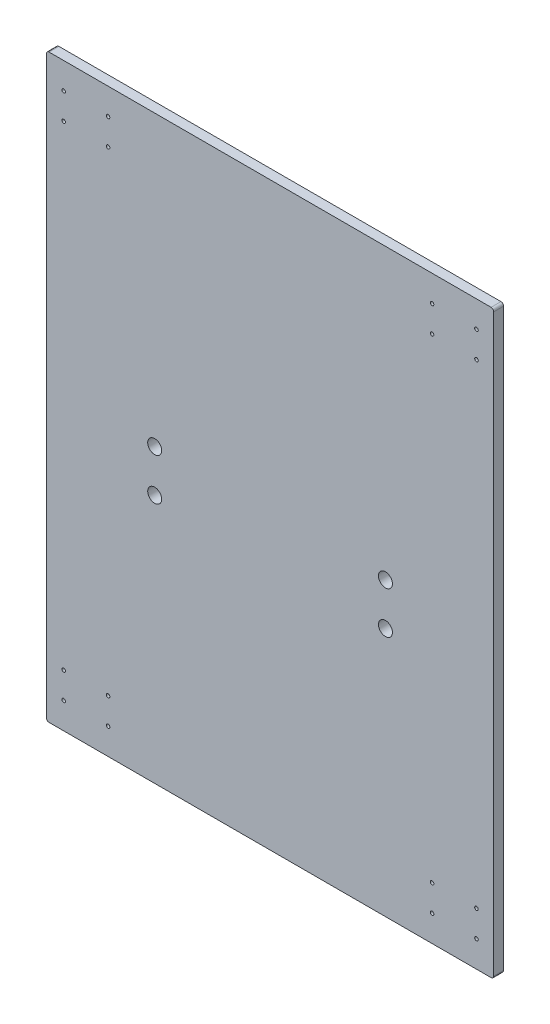
SolidWorks part; units mm, degrees
material "Plain Carbon Steel"
ref_plane "Front Plane" through (0, 0, 0) normal (0, 0, 1) x (1, 0, 0)
ref_plane "Top Plane" through (0, 0, 0) normal (0, 1, 0) x (1, 0, 0)
ref_plane "Right Plane" through (0, 0, 0) normal (1, 0, 0) x (0, 0, -1)
sketch "Sketch1" plane through (0, 0, 0) normal (0, 0, 1) x (1, 0, 0)
  line L1 (0, 0) -> (0, 38.1) construction
  line L2 (393.7, -522.2875) -> (-38.1, -522.2875)
  line L3 (393.7, -522.2875) -> (393.7, 38.1)
  line L4 (393.7, 38.1) -> (-38.1, 38.1)
  line L5 (-38.1, -522.2875) -> (-38.1, 38.1)
  line L6 (393.7, -522.2875) -> (-38.1, 38.1) construction
  line L7 (393.7, 38.1) -> (-38.1, -522.2875) construction
  line L9 (0, 0) -> (-38.1, 0) construction
  line L10 (-25.4, -21.4312) -> (-25.4, 21.4312) construction
  point P4 (177.8, -242.0937)
  dimension "D1" = 12.7
extrude "Boss-Extrude1" add sketch "Sketch1" along normal blind 9.525
fillet "Fillet1" radius 2.54 4 edges at (393.7, 38.1, 4.7625) (393.7, -522.2875, 4.7625) (-38.1, -522.2875, 4.7625) (-38.1, 38.1, 4.7625)
sketch "Sketch3" plane through (0, 0, 0) normal (0, 0, -1) x (-1, 0, 0)
  line L0 (-177.8, 38.1) -> (-177.8, -522.2875) construction
  line L1 (-391.16, 38.1) -> (35.56, 38.1) construction
  line L2 (35.56, -522.2875) -> (-391.16, -522.2875) construction
  line L3 (-177.8, -261.0637) -> (-289.1714, -261.0637) construction
  line L4 (-289.1714, -240.7437) -> (-289.1714, -281.3837) construction
  point P8 (-289.1714, -240.7437)
  point P9 (-289.1714, -281.3837)
  point P13 (-66.4286, -281.3837)
  point P14 (-66.4286, -240.7437)
  dimension "D1" = 40.64
  dimension "D2" = 240.9038
  dimension "D3" = 222.7428
hole_wizard "1/2 Clearance Hole1" positions "Sketch3" profile "Sketch4" hole size "1/2" standard "ANSI Inch" end condition up to next
sketch "Sketch4" plane through (66.4286, -240.7437, 0) normal (1, 0, 0) x (0, 1, 0)
  line L0 (0, 0) -> (0, 9.525)
  line L1 (0, 9.525) -> (6.7462, 9.525)
  line L2 (6.7462, 9.525) -> (6.7462, 0)
  line L5 (6.7462, 0) -> (0, 0)
  line L11 (0, -6.35) -> (0, 107.95) construction
  dimension "Thru Hole Dia." = 13.4925
  dimension "Thru Hole Depth" = 9.525
sketch "Sketch6" plane through (0, 0, 0) normal (0, 0, -1) x (-1, 0, 0)
  line L0 (-393.7, -519.7475) -> (-393.7, 35.56) construction
  line L1 (-391.16, 38.1) -> (35.56, 38.1) construction
  line L2 (-177.8, 38.1) -> (-177.8, -522.2875) construction
  line L3 (35.56, -522.2875) -> (-391.16, -522.2875) construction
  line L4 (38.1, -242.0937) -> (-393.7, -242.0938) construction
  line L5 (38.1, 35.56) -> (38.1, -519.7475) construction
  point P0 (-377.0376, 12.7)
  point P1 (-377.0376, -12.7)
  point P2 (-334.1624, 12.7)
  point P3 (-334.1624, -12.7)
  point P16 (-21.4376, -12.7)
  point P17 (21.4376, -12.7)
  point P18 (21.4376, 12.7)
  point P19 (-21.4376, 12.7)
  point P20 (-21.4376, -496.8875)
  point P21 (21.4376, -496.8875)
  point P22 (21.4376, -471.4875)
  point P23 (-21.4376, -471.4875)
  point P24 (-334.1624, -471.4875)
  point P25 (-334.1624, -496.8875)
  point P26 (-377.0376, -471.4875)
  point P27 (-377.0376, -496.8875)
  dimension "D1" = 16.6624
  dimension "D2" = 25.4
  dimension "D3" = 25.4
  dimension "D4" = 42.8752
hole_wizard "#5 Clearance Hole1" positions "Sketch6" profile "Sketch7" hole size "#5" standard "ANSI Inch" end condition up to next
sketch "Sketch7" plane through (377.0376, 12.7, 0) normal (1, 0, 0) x (0, 1, 0)
  line L0 (0, 0) -> (0, 9.525)
  line L1 (0, 9.525) -> (1.7272, 9.525)
  line L2 (1.7272, 9.525) -> (1.7272, 0)
  line L5 (1.7272, 0) -> (0, 0)
  line L11 (0, -6.35) -> (0, 107.95) construction
  dimension "Thru Hole Dia." = 3.4544
  dimension "Thru Hole Depth" = 9.525
